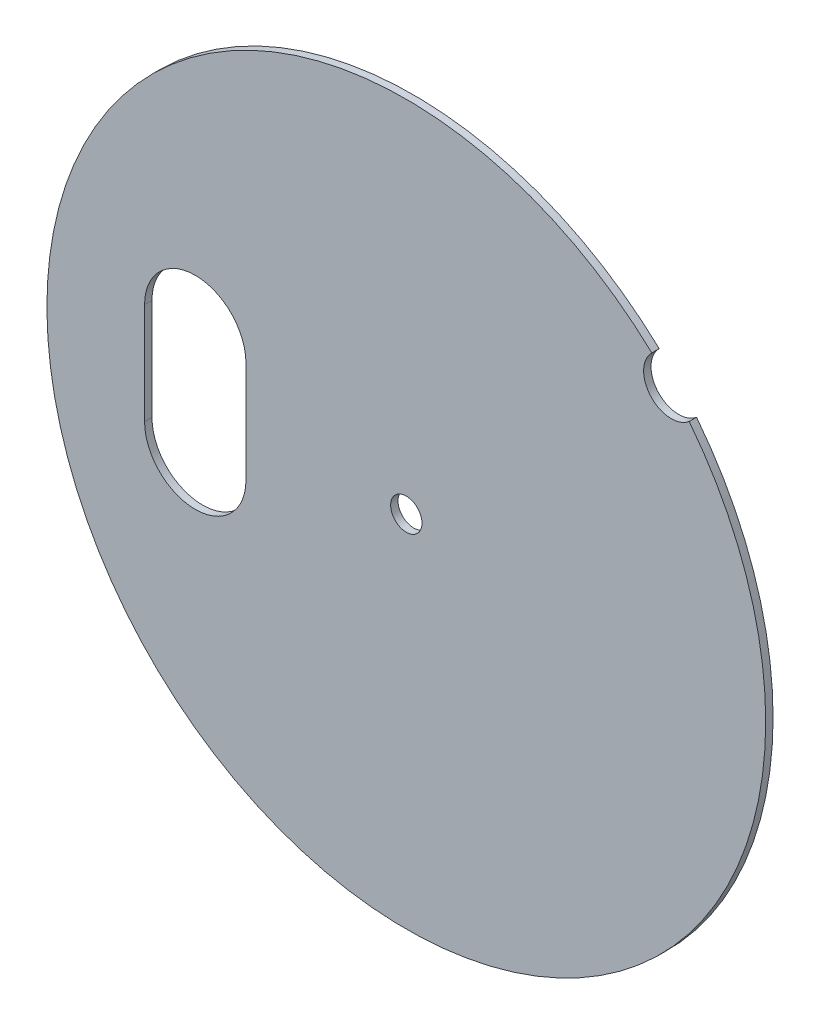
SolidWorks part; units mm, degrees
ref_plane "Plan de face" through (0, 0, 0) normal (0, 0, 1) x (1, 0, 0)
ref_plane "Plan de dessus" through (0, 0, 0) normal (0, 1, 0) x (1, 0, 0)
ref_plane "Plan de droite" through (0, 0, 0) normal (1, 0, 0) x (0, 0, -1)
sketch "Esquisse1" plane through (0, 0, 0) normal (0, 0, 1) x (1, 0, 0)
  line L0 (0, 0) -> (19.5, 0) construction
  line L1 (0, 19.5) -> (0, 0) construction
  line L2 (-6.7, -3.3481) -> (-6.7, 3.3481) construction
  line L3 (-11.45, -2.75) -> (-11.45, 2.75) construction
  line L4 (-14.2, -2.75) -> (-14.2, 2.75)
  line L5 (-8.7, -2.75) -> (-8.7, 2.75)
  line L6 (-11.45, 0) -> (0, 0) construction
  line L7 (0, 0) -> (14.3769, 13.174) construction
  arc A0 (13.3217, 14.2401) -> (15.347, 12.0299) centre (0, 0) ccw
  circle A4 centre (0, 0) radius 0.85
  arc A5 (13.3217, 14.2401) -> (15.347, 12.0299) centre (14.3769, 13.174) ccw
  arc A6 (-14.2, -2.75) -> (-8.7, -2.75) centre (-11.45, -2.75) ccw
  arc A7 (-8.7, 2.75) -> (-14.2, 2.75) centre (-11.45, 2.75) ccw
  point P5 (8.234, -1.9)
  point P6 (-7.9, -3)
  point P10 (17.506, 8.5901)
  point P11 (-11.45, 0)
  point P20 (-11.45, 0)
  dimension "D1" = 39
  dimension "D6" = 5.5
  dimension "D8" = 42.5
  dimension "D10" = 1.7
  dimension "D7" = 5.5
  dimension "D9" = 1.5
  dimension "D2" = 1.9
  dimension "D3" = 3
  dimension "D4" = 7.9
  dimension "D5" = 8.234
  dimension "D11" = 2
  dimension "D13" = 19.5
extrude "Boss.-Extru.1" add sketch "Esquisse1" along normal blind 0.4
